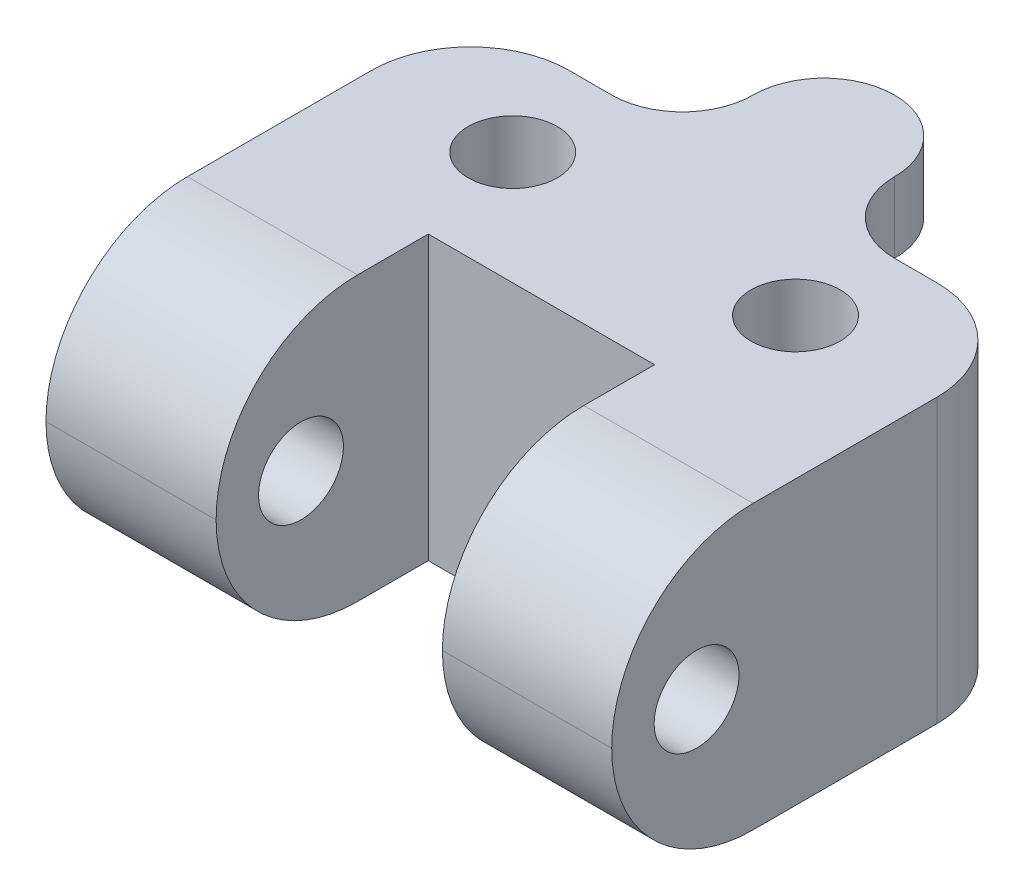
SolidWorks part; units mm, degrees
ref_plane "Front Plane" through (0, 0, 0) normal (0, 0, 1) x (1, 0, 0)
ref_plane "Top Plane" through (0, 0, 0) normal (0, 1, 0) x (1, 0, 0)
ref_plane "Right Plane" through (0, 0, 0) normal (1, 0, 0) x (0, 0, -1)
sketch "Sketch1" plane through (0, 0, 0) normal (0, 1, 0) x (1, 0, 0)
  line L1 (0, 0) -> (40, 0)
  line L2 (0, 0) -> (0, 30)
  line L3 (0, 30) -> (40, 30)
  line L4 (40, 0) -> (40, 30)
  dimension "D1" = 40
  dimension "D2" = 30
extrude "Boss-Extrude1" add sketch "Sketch1" along normal blind 20
sketch "Sketch2" plane through (0, 20, 0) normal (0, 1, 0) x (1, 0, 0)
  line L5 (0, 0) -> (40, 0) construction
  line L12 (12.0295, 15) -> (28.0295, 15)
  line L13 (12.0295, 15) -> (12.0295, 0)
  line L14 (12.0295, 0) -> (28.0295, 0)
  line L15 (28.0295, 15) -> (28.0295, 0)
  circle A0 centre (10, 23) radius 3.15
  circle A1 centre (30, 23) radius 3.15
  dimension "D1" = 6.3
  dimension "D3" = 6.3
  dimension "D2" = 15
extrude "Cut-Extrude1" cut sketch "Sketch2" against normal blind 20
sketch "Sketch3" plane through (0, 0, -30) normal (0, 0, -1) x (-1, 0, 0)
  line L0 (-40, 20) -> (0, 20) construction
  line L1 (-25, 20) -> (-15, 20)
  line L2 (-25, 20) -> (-25, 15)
  line L3 (-25, 15) -> (-15, 15)
  line L4 (-15, 20) -> (-15, 15)
extrude "Boss-Extrude2" add sketch "Sketch3" along normal blind 10
fillet "Fillet3" radius 5 2 edges at (25, 17.5, -30) (15, 17.5, -30)
fillet "Fillet4" radius 5 1 edges at (20, 15, -30)
sketch "Sketch6" plane through (0, 0, 0) normal (-1, 0, 0) x (0, 0, 1)
  circle A0 centre (-6, 10) radius 3
extrude "Cut-Extrude3" cut sketch "Sketch6" against normal blind 140
fillet "Fillet5" radius 10 4 edges at (34.0148, 20, 0) (34.0148, 0, 0) (6.0148, 0, 0) (6.0148, 20, 0)
fillet "Fillet6" radius 5 2 edges at (25, 17.5, -40) (15, 17.5, -40)
fillet "Fillet7" radius 7 2 edges at (40, 10, -30) (0, 10, -30)
